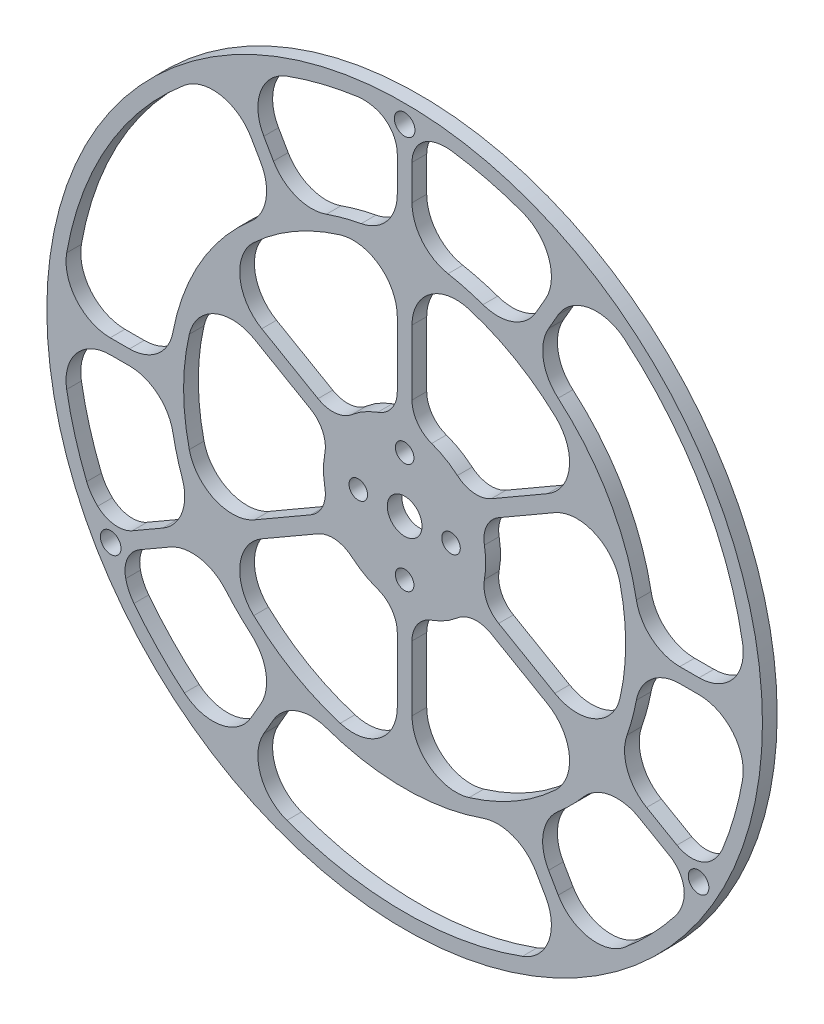
SolidWorks part; units mm, degrees
ref_plane "Front Plane" through (0, 0, 0) normal (0, 0, 1) x (1, 0, 0)
ref_plane "Top Plane" through (0, 0, 0) normal (0, 1, 0) x (1, 0, 0)
ref_plane "Right Plane" through (0, 0, 0) normal (1, 0, 0) x (0, 0, -1)
sketch "Sketch1" plane through (0, 0, 0) normal (0, 0, 1) x (1, 0, 0)
  line L2 (-1.905, 56.642) -> (1.905, 56.642)
  line L3 (-1.905, 56.642) -> (-1.905, 60.452)
  line L4 (-1.905, 60.452) -> (1.905, 60.452)
  line L5 (1.905, 56.642) -> (1.905, 60.452)
  line L6 (-1.905, 56.642) -> (1.905, 60.452) construction
  line L7 (-1.905, 60.452) -> (1.905, 56.642) construction
  line L9 (50.0059, -26.6712) -> (48.1009, -29.9708)
  line L10 (50.0059, -26.6712) -> (53.3055, -28.5762)
  line L11 (53.3055, -28.5762) -> (51.4005, -31.8758)
  line L12 (48.1009, -29.9708) -> (51.4005, -31.8758)
  line L14 (-48.1009, -29.9708) -> (-50.0059, -26.6712)
  line L15 (-48.1009, -29.9708) -> (-51.4005, -31.8758)
  line L16 (-51.4005, -31.8758) -> (-53.3055, -28.5762)
  line L17 (-50.0059, -26.6712) -> (-53.3055, -28.5762)
  line L19 (0, 14) -> (0, -14) construction
  line L20 (0, -14) -> (14, 0) construction
  line L21 (14, 0) -> (-14, 0) construction
  line L22 (0, 14) -> (0, 39.4)
  line L24 (12.1244, 7) -> (34.1214, 19.7)
  line L26 (0, -14) -> (0, -39.4)
  line L27 (-12.1244, -7) -> (-49.0534, -28.321)
  line L28 (-12.1244, 7) -> (-34.1214, 19.7)
  line L30 (19.7042, 34.119) -> (30.226, 52.353)
  line L31 (39.4, -0.0049) -> (60.452, 0)
  line L32 (19.6958, -34.1238) -> (30.226, -52.353)
  line L33 (-19.7042, -34.119) -> (-30.226, -52.353)
  line L34 (-39.4, 0.0049) -> (-60.452, 0)
  line L35 (-19.6958, 34.1238) -> (-30.226, 52.353)
  line L36 (0, 14) -> (0, 56.642)
  line L37 (12.1244, -7) -> (49.0534, -28.321)
  line L39 (-12.1244, -7) -> (-34.1214, -19.7) [skipped]
  line L40 (12.1244, -7) -> (34.1214, -19.7) [skipped]
  circle A1 centre (0, 58.547) radius 1.778
  circle A2 centre (50.7032, -29.2735) radius 1.778
  circle A3 centre (-50.7032, -29.2735) radius 1.778
  circle A4 centre (0, 0) radius 60.452
  circle A5 centre (0, 0) radius 14
  circle A6 centre (0, 9.5) radius 1.6
  circle A7 centre (0, -9.5) radius 1.6
  circle A8 centre (8, 0) radius 1.6
  circle A9 centre (-8, 0) radius 1.6
  circle A10 centre (0, 0) radius 3
  circle A11 centre (0, 0) radius 39.4
  circle A12 centre (0, 0) radius 60.452
  circle A13 centre (0, 0) radius 60.452
  circle A14 centre (0, 0) radius 60.452
  circle A15 centre (0, 0) radius 60.452
  circle A16 centre (0, 0) radius 60.452
  point P3 (0, 58.547)
  point P27 (0, 0)
  point P55 (0, 0)
  point P73 (0, 0)
  dimension "D3" = 3.556
  dimension "D4" = 28
  dimension "D5" = 8
  dimension "D6" = 8
  dimension "D7" = 9.5
  dimension "D8" = 9.5
  dimension "D9" = 3.2
  dimension "D10" = 3.2
  dimension "D11" = 3.2
  dimension "D12" = 3.2
  dimension "D13" = 6
  dimension "D14" = 25.4
  dimension "D2" = 3.81
  dimension ".15" = 3.81
  dimension "D15" = 6
  dimension "D17" = 3
extrude "Extrude-Thin1" add sketch "Sketch1" along normal blind 2.54 thin contours L37 | L31 | L32 | L33 | L27 | L34 | L26 | L28 | L24 | L35 | L30 | A4 | A11 thin type mid plane wall 2.54
extrude "Boss-Extrude1" add sketch "Sketch1<14>" along normal blind 2.54 contours L5 A4 L3 L2 A1 | L12 A4 L10 L9 A2 | L17 A4 L15 L14 A3 | A5 A10 A9 A8 A7 A6 region at (-1.8511, 58.532, 0) region at (6.802, 11.7814, 0) region at (-51.606, -27.6797, 0) region at (52.7587, -29.3616, 0)
sketch "Sketch1<14>" plane through (0, 0, 0) normal (0, 0, 1) x (1, 0, 0) same geometry as "Sketch1"
sketch "Sketch2" plane through (0, 0, 2.54) normal (0, 0, 1) x (1, 0, 0)
  line L0 (0, 56.642) -> (0, 14)
  line L1 (-1.905, 56.642) -> (1.905, 56.642) construction
  circle A0 centre (0, 0) radius 14 construction
extrude "Extrude-Thin3" add sketch "Sketch2" against normal blind 2.54 thin contours L0 thin type mid plane wall 2.54
extrude "Cut-Extrude2" cut sketch "Sketch1<16>" against normal blind 2.54 and the other way through all contours A1 | A1 | A3 | A2 region at (0, 58.547, 0)
sketch "Sketch1<16>" plane through (0, 0, 0) normal (0, 0, 1) x (1, 0, 0) same geometry as "Sketch1"
fillet "Fillet1" radius 7.62 54 edges at (1.27, 56.642, 1.27) (1.905, 59.1513, 1.27) (-1.27, 56.642, 1.27) (-1.905, 59.1513, 1.27) (50.2741, -31.2254, 1.27) (48.4184, -29.4209, 1.27) (49.6884, -27.2211, 1.27) (52.1791, -27.9259, 1.27) (-49.6884, -27.2211, 1.27) (-52.1791, -27.9259, 1.27) (-48.4184, -29.4209, 1.27) (-50.2741, -31.2254, 1.27) (-40.65, 1.2746, 1.27) (-59.1684, 1.2703, 1.27) (-59.1684, -1.2697, 1.27) (-35.8391, -19.2252, 1.27) (-40.6503, -1.2654, 1.27) (-30.6843, -50.6062, 1.27) (-21.4288, -34.5667, 1.27) (-34.5691, -21.4249, 1.27) (-28.4846, -51.8762, 1.27) (-19.2293, -35.8369, 1.27) (28.4841, -51.8765, 1.27) (30.6838, -50.6065, 1.27) (19.2212, -35.8412, 1.27) (21.421, -34.5715, 1.27) (34.5691, -21.4249, 1.27) (35.8391, -19.2252, 1.27) (59.1684, 1.2697, 1.27) (59.1684, -1.2703, 1.27) (40.6503, 1.2654, 1.27) (40.65, -1.2746, 1.27) (28.4846, 51.8762, 1.27) (19.2293, 35.8369, 1.27) (21.4288, 34.5667, 1.27) (30.6843, 50.6062, 1.27) (1.27, 40.6502, 1.27) (-1.27, 40.6502, 1.27) (-19.2212, 35.8412, 1.27) (-21.421, 34.5715, 1.27) (-28.4841, 51.8765, 1.27) (-30.6838, 50.6065, 1.27) (-33.6382, -17.9546, 1.27) (-32.3682, -20.1543, 1.27) (-1.27, -38.1088, 1.27) (1.27, -38.1088, 1.27) (32.3682, -20.1543, 1.27) (33.6382, -17.9546, 1.27) (33.6382, 17.9546, 1.27) (32.3682, 20.1543, 1.27) (-33.6382, 17.9546, 1.27) (-32.3682, 20.1543, 1.27) (1.27, 38.1088, 1.27) (-1.27, 38.1088, 1.27)
sketch "Sketch3" plane through (0, 0, 2.54) normal (0, 0, 1) x (1, 0, 0)
  line L0 (-1.27, 15.3211) -> (1.27, 15.3211)
  line L1 (-1.27, 15.3211) -> (-1.27, 12.1984)
  line L2 (1.27, 15.3211) -> (1.27, 12.1984)
  line L3 (-1.27, 12.1984) -> (1.27, 12.1984)
  line L4 (-1.27, 29.1861) -> (-1.27, 14) construction
  line L5 (1.27, 29.1861) -> (1.27, 14) construction
  line L6 (12.6334, 8.7604) -> (13.9034, 6.5607)
  line L7 (12.6334, 8.7604) -> (9.9291, 7.199)
  line L8 (9.9291, 7.199) -> (11.1991, 4.9993)
  line L9 (13.9034, 6.5607) -> (11.1991, 4.9993)
  line L10 (13.9034, -6.5607) -> (12.6334, -8.7604)
  line L11 (13.9034, -6.5607) -> (11.1991, -4.9993)
  line L12 (11.1991, -4.9993) -> (9.9291, -7.199)
  line L13 (12.6334, -8.7604) -> (9.9291, -7.199)
  line L14 (1.27, -15.3211) -> (-1.27, -15.3211)
  line L15 (1.27, -15.3211) -> (1.27, -12.1984)
  line L16 (1.27, -12.1984) -> (-1.27, -12.1984)
  line L17 (-1.27, -15.3211) -> (-1.27, -12.1984)
  line L18 (-12.6334, -8.7604) -> (-13.9034, -6.5607)
  line L19 (-12.6334, -8.7604) -> (-9.9291, -7.199)
  line L20 (-9.9291, -7.199) -> (-11.1991, -4.9993)
  line L21 (-13.9034, -6.5607) -> (-11.1991, -4.9993)
  line L22 (-13.9034, 6.5607) -> (-12.6334, 8.7604)
  line L23 (-13.9034, 6.5607) -> (-11.1991, 4.9993)
  line L24 (-11.1991, 4.9993) -> (-9.9291, 7.199)
  line L25 (-12.6334, 8.7604) -> (-9.9291, 7.199)
  point P30 (0, 0)
  dimension "D1" = 6
extrude "Boss-Extrude2" add sketch "Sketch3" against normal blind 2.54
fillet "Fillet2" radius 5.08 18 edges at (1.27, -13.9423, 1.27) (-1.27, -13.9423, 1.27) (-12.7094, -5.8713, 1.27) (-11.4394, -8.071, 1.27) (-11.4394, 8.071, 1.27) (-12.7094, 5.8713, 1.27) (-1.27, 13.9423, 1.27) (1.27, 13.9423, 1.27) (11.4394, -8.071, 1.27) (12.7094, -5.8713, 1.27) (12.7094, 5.8713, 1.27) (11.4394, 8.071, 1.27) (48.1009, -29.9708, 1.27) (50.0059, -26.6712, 1.27) (1.905, 56.642, 1.27) (-1.905, 56.642, 1.27) (-50.0059, -26.6712, 1.27) (-48.1009, -29.9708, 1.27)
